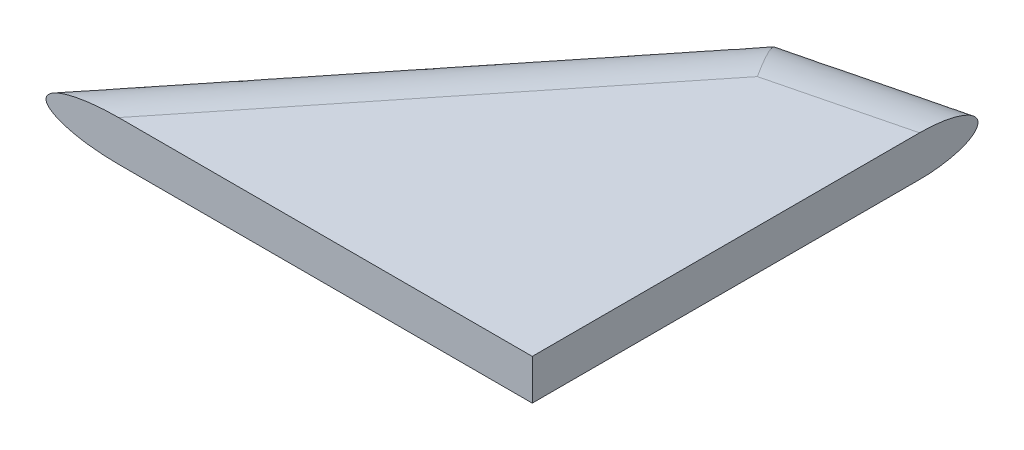
SolidWorks part; units mm, degrees
ref_plane "Front Plane" through (0, 0, 0) normal (0, 0, 1) x (1, 0, 0)
ref_plane "Top Plane" through (0, 0, 0) normal (0, 1, 0) x (1, 0, 0)
ref_plane "Right Plane" through (0, 0, 0) normal (1, 0, 0) x (0, 0, -1)
sketch "Sketch1" plane through (0, 0, 0) normal (0, 1, 0) x (1, 0, 0)
  line L0 (0, 0) -> (40, 50)
  line L1 (40, 50) -> (60, 55)
  line L2 (60, 55) -> (60, 0)
  line L3 (60, 0) -> (0, 0)
  dimension "D1" = 60
  dimension "D2" = 55
  dimension "D3" = 40
  dimension "D4" = 50
extrude "Boss-Extrude1" add sketch "Sketch1" along normal mid plane 5
fillet "Fillet3" radius 2.5 2 edges at (20, 2.5, -25) (50, 2.5, -52.5) second distance 7 first distance on face at (20, 0, -25) first distance on face at (50, 0, -52.5)
fillet "Fillet4" radius 2.5 2 edges at (20, -2.5, -25) (50, -2.5, -52.5) second distance 7 first distance on face at (15, -0.625, -18.75) first distance on face at (47.5, -0.625, -51.875)
